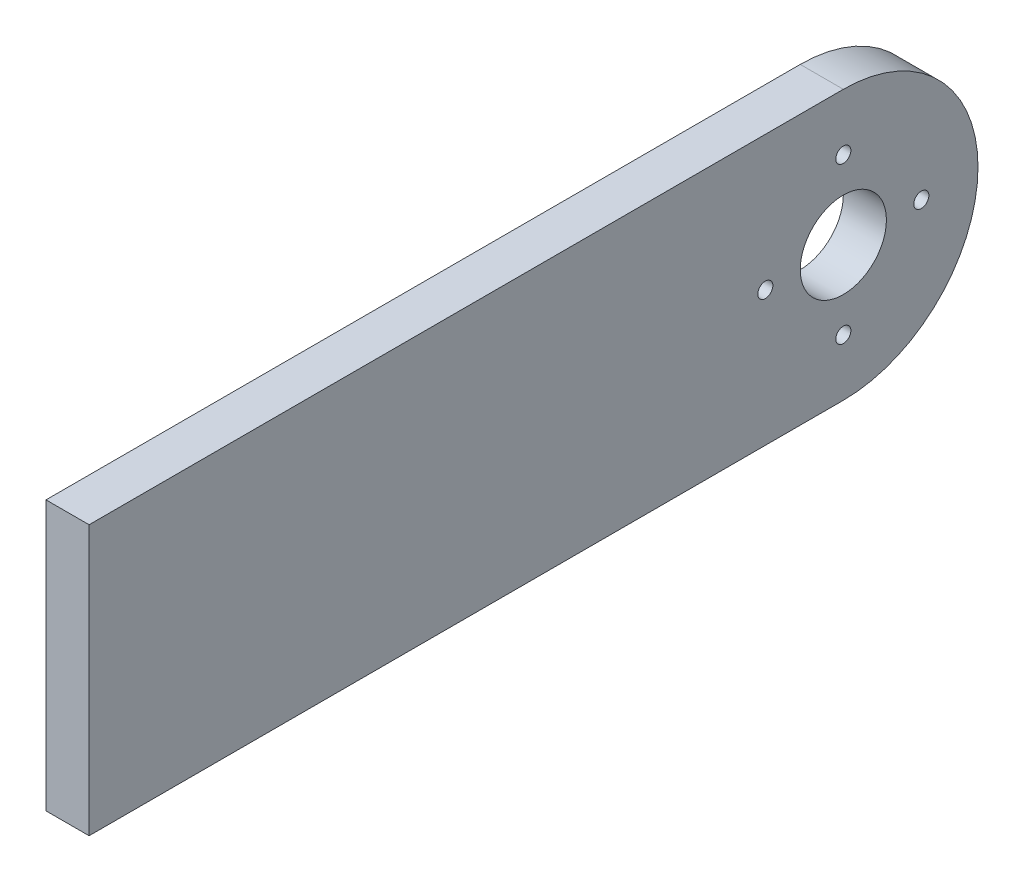
SolidWorks part; units mm, degrees
material "Perspex (TM) GS Acrylic Cast Sheet"
ref_plane "Front Plane" through (0, 0, 0) normal (0, 0, 1) x (1, 0, 0)
ref_plane "Top Plane" through (0, 0, 0) normal (0, 1, 0) x (1, 0, 0)
ref_plane "Right Plane" through (0, 0, 0) normal (1, 0, 0) x (0, 0, -1)
sketch "Sketch1" plane through (0, 0, 0) normal (1, 0, 0) x (0, 0, -1)
  line L0 (-70, 12.5) -> (-70, -12.5)
  line L19 (-70, 12.5) -> (0, 12.5)
  line L20 (-70, -12.5) -> (0, -12.5)
  circle A0 centre (0, 0) radius 4
  circle A1 centre (-7.24, 0) radius 0.7
  circle A2 centre (0, 7.24) radius 0.7
  circle A3 centre (7.24, 0) radius 0.7
  circle A4 centre (0, -7.24) radius 0.7
  arc A5 (0, -12.5) -> (0, 12.5) centre (0, 0) ccw
  point P18 (0, 0)
  dimension "D1" = 8
  dimension "D2" = 1.4
  dimension "D5" = 70
  dimension "D9" = 25
  dimension "D3" = 7.24
  dimension "D4" = 4
extrude "Boss-Extrude1" add sketch "Sketch1" along normal blind 4
sketch "Sketch2" plane through (4, 0, 0) normal (1, 0, 0) x (0, 0, -1)
  line L0 (0, 0) -> (-70, 0) construction
  line L1 (-70, 12.5) -> (-70, -12.5) construction
